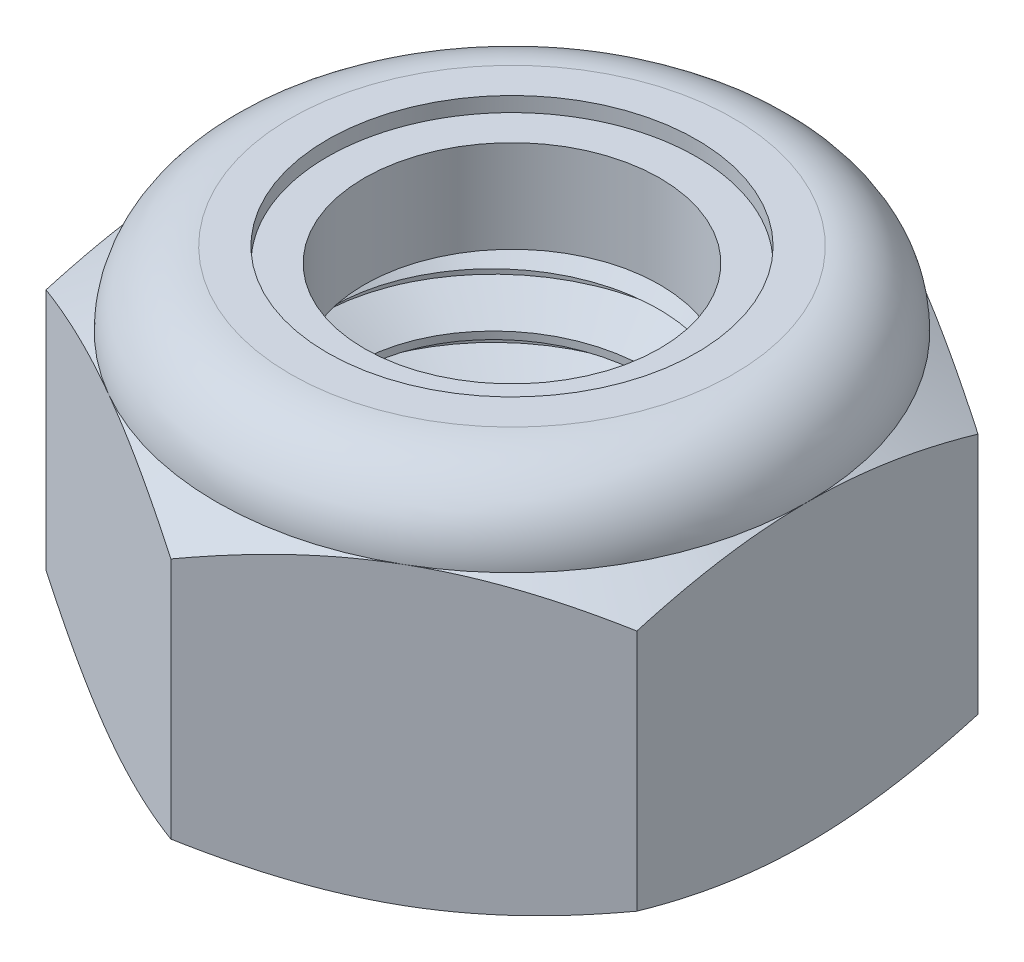
SolidWorks part; units mm, degrees
ref_plane "Front" through (0, 0, 0) normal (0, 0, 1) x (1, 0, 0)
ref_plane "Top" through (0, 0, 0) normal (0, 1, 0) x (1, 0, 0)
ref_plane "Right" through (0, 0, 0) normal (1, 0, 0) x (0, 0, -1)
sketch "Sketch1" plane through (0, 0, 0) normal (0, 1, 0) x (1, 0, 0)
  line L1 (0, 4.6188) -> (-4, 2.3094) construction
  line L2 (-4, 2.3094) -> (-4, -2.3094) construction
  line L3 (-4, -2.3094) -> (0, -4.6188) construction
  line L4 (0, -4.6188) -> (4, -2.3094) construction
  line L5 (4, -2.3094) -> (4, 2.3094) construction
  line L6 (4, 2.3094) -> (0, 4.6188) construction
  circle A0 centre (0, 0) radius 4 construction
  circle A1 centre (0, 0) radius 2.5 construction
  point P11 (0, -2.5)
  point P12 (0, 0)
  dimension "Thread Dia" = 5
  dimension "Width" = 8
sketch "Sketch2" plane through (0, 0, 0) normal (1, 0, 0) x (0, 0, -1)
  line L0 (-2.5, -2.5) -> (-2.5, 2.5) construction
  line L1 (0, 0) -> (0, 2.5) construction
  line L2 (0, 2.5) -> (-2.5, 2.5) construction
  line L3 (-2.5866, -2.45) -> (-1.8938, -2.85) construction
  line L4 (-1.8938, -2.85) -> (-2.5866, -3.25) construction
  line L5 (-2.5866, -3.25) -> (-2.5866, -2.45) construction
  line L6 (-1.9804, -2.8) -> (-1.9804, -2.9) construction
  line L7 (-2.5433, -2.85) -> (-2.5433, -2.475) construction
  line L8 (-2.5, -2.5) -> (-2.5, -3.2) construction
  line L9 (-2.5866, -2.85) -> (-2.5, -2.85) construction
  line L10 (-1.9804, -2.85) -> (-1.8938, -2.85) construction
  line L11 (-2.5433, -2.85) -> (-2.5433, -3.225) construction
  line L12 (-2, 1.05) -> (-2, 2.3) construction
  line L13 (-2, 2.3) -> (-2.5, 2.3) construction
  line L14 (-2.5, 2.3) -> (-2.5, 1.05) construction
  line L15 (-2.5, 1.05) -> (-2, 1.05) construction
  point P6 (-2.5, 0)
  point P25 (-2, 2.3)
  dimension "Height" = 5
  dimension "Pitch" = 0.8
  dimension "D2" = 0.1
  dimension "D1" = 0.5
  dimension "D3" = 1.25
  dimension "D4" = 0.2
sketch "Sketch3" plane through (0, 0, 0) normal (0, 1, 0) x (1, 0, 0)
  line L0 (0, 4.6188) -> (4, 2.3094)
  line L1 (4, 2.3094) -> (4, -2.3094)
  line L2 (4, -2.3094) -> (0, -4.6188)
  line L3 (0, -4.6188) -> (-4, -2.3094)
  line L4 (-4, -2.3094) -> (-4, 2.3094)
  line L5 (-4, 2.3094) -> (0, 4.6188)
sketch "Sketch7" plane through (0, 0, 0) normal (0, 1, 0) x (1, 0, 0)
  circle A0 centre (0, 0) radius 4 construction
  circle A1 centre (0, 0) radius 4
extrude "Boss-Extrude2" add sketch "Sketch3" along normal up to vertex (-2.5 mm away) and the other way up to vertex (2.5 mm away) up to point (0, -2.5, 2.5) other way up to point (0, -2.5, 2.5)
sketch "Sketch4" plane through (0, 0, 0) normal (0, 1, 0) x (1, 0, 0)
  circle A0 centre (0, 0) radius 2.5
  circle A1 centre (0, 0) radius 2.5 construction
extrude "Cut-Extrude4" cut sketch "Sketch4" along normal through all both and the other way through all
sketch "Sketch6" plane through (0, 0, 0) normal (1, 0, 0) x (0, 0, -1)
  line L0 (4, -2.5) -> (4, 2.5) construction
  line L7 (4, 2.5) -> (4, 1.5) construction
  line L8 (4, 2.5) -> (3, 2.5) construction
  line L11 (4, 1.5) -> (4.6188, 1.5)
  line L13 (4.6188, 1.5) -> (4.6188, 2.5)
  line L14 (4.6188, 2.5) -> (3, 2.5)
  arc A1 (4, 1.5) -> (3, 2.5) centre (3, 1.5) ccw
  point P15 (4, 0)
  dimension "D1" = 1
revolve "Cut-Revolve1" cut sketch "Sketch6" angle 360 about axis through (0, 2.5, 0) along (0, -1, 0)
extrude "Cut-Extrude5" cut sketch "Sketch7" against normal through all draft 60 from surface flip side to cut starting at face at (0, 1.5, -4.0276)
sketch "Sketch19" plane through (0, -2.5, 0) normal (0, -1, 0) x (1, 0, 0)
  circle A0 centre (0, 0) radius 4 construction
  circle A1 centre (0, 0) radius 4
extrude "Cut-Extrude6" cut sketch "Sketch19" against normal through all draft 60 flip side to cut
chamfer "Chamfer1" distance 0.3 angle 45 1 edges at (0, -2.5, 2.5)
sketch "Sketch24" plane through (0, 0, 0) normal (1, 0, 0) x (0, 0, -1)
  line L0 (-2.5, 2.3) -> (-2, 2.3)
  line L1 (-2, 2.3) -> (-2, 1.05)
  line L2 (-2, 1.05) -> (-2.5, 1.05)
  line L3 (-2.5, 1.05) -> (-2.5, 2.3)
revolve "Revolve1" add sketch "Sketch24" angle 360 about L1
ref_plane "Contact Plane 1" through (0, 2.5, 0) normal (0, 1, 0) x (1, 0, 0)
ref_plane "Contact Plane 2" through (0, -2.5, 0) normal (0, -1, 0) x (-1, 0, 0)
sketch "Sketch5" plane through (0, -2.5, 0) normal (0, 1, 0) x (1, 0, 0)
  circle A1 centre (0, 0) radius 2.5
  circle A2 centre (0, 0) radius 2.5 construction
curve "Helix/Spiral1" pitch 0.8 height 5 radius 2.5 centre (0, -2.5, 0) axis (0, 1, 0) start towards (0, 0, 1)
sketch "Sketch21" plane through (0, 0, 0) normal (1, 0, 0) x (0, 0, -1)
  line L0 (-2.5433, -2.475) -> (-2.5433, -3.225)
  line L1 (-2.5433, -3.225) -> (-1.9804, -2.9)
  line L2 (-1.9804, -2.9) -> (-1.9804, -2.8)
  line L3 (-1.9804, -2.8) -> (-2.5433, -2.475)
sweep "Sweep1" add profiles "Sketch21" path "Helix/Spiral1"
sketch "Sketch23" plane through (0, 1.05, 0) normal (0, 1, 0) x (1, 0, 0)
  line L0 (0, 0) -> (0, -2.5) construction
  circle A1 centre (0, 0) radius 2.5866
extrude "Cut-Extrude8" cut sketch "Sketch23" along normal through all and the other way through all draft 45
combine bodies "Combine1" operation type add bodies to combine 147 143
sketch "Sketch30" plane through (0, -2.5, 0) normal (0, -1, 0) x (1, 0, 0)
  circle A0 centre (0, 0) radius 2.8 construction
  circle A1 centre (0, 0) radius 2.8
extrude "Cut-Extrude12" cut sketch "Sketch30" along normal through all and the other way through all draft 45
equation "\"D2@Sketch2\" = \"Pitch@Sketch2\" / 8"
equation "\"D1@Sketch2\"=\"Pitch@Sketch2\"*.625"
equation "\"D3@Sketch2\"=\"Height@Sketch2\"/4"
equation "\"D4@Sketch2\"=\"Pitch@Sketch2\"/4"
equation "\"D4@Helix/Spiral1\"=\"Pitch@Sketch2\""
equation "\"D3@Helix/Spiral1\"=\"Height@Sketch2\""
equation "\"D1@Sketch6\"=\"Pitch@Sketch2\"*1.25"
equation "\"D1@Chamfer1\"=\"Pitch@Sketch2\"*.375"
